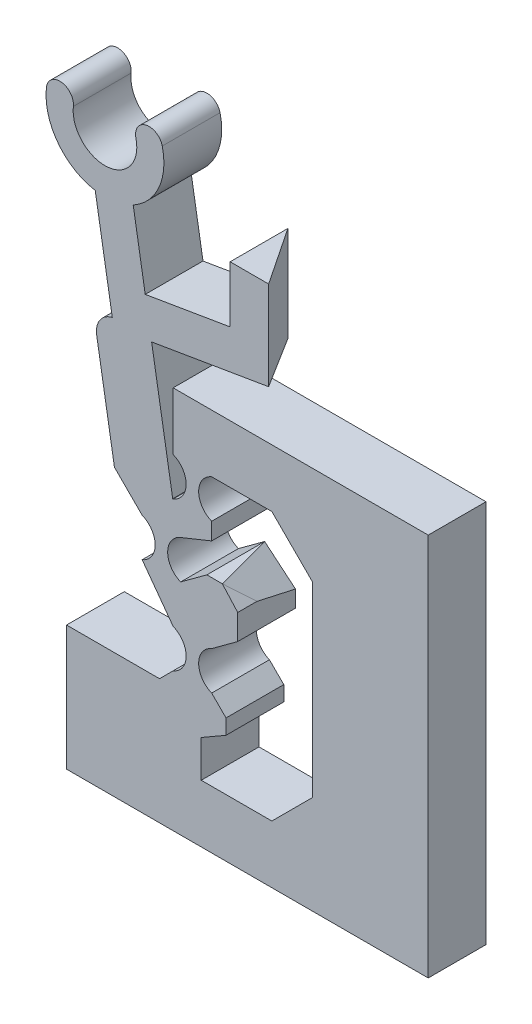
SolidWorks part; units mm, degrees
ref_plane "Front Plane" through (0, 0, 0) normal (0, 0, 1) x (1, 0, 0)
ref_plane "Top Plane" through (0, 0, 0) normal (0, 1, 0) x (1, 0, 0)
ref_plane "Right Plane" through (0, 0, 0) normal (1, 0, 0) x (0, 0, -1)
sketch "Sketch-SkeletonConfigUp" plane through (0, 0, 0) normal (0, 0, 1) x (1, 0, 0)
  line L0 (0, 0) -> (0, -50000) construction
  line L1 (0, 0) -> (4.5811, 6.2164) construction
  line L2 (9.8143, 13.3177) -> (4.5811, 13.945) construction
  line L3 (4.5811, 13.945) -> (2.9713, 10.4094) construction
  line L4 (2.9713, 10.4094) -> (4.5811, 6.2164) construction
  line L5 (4.5811, 13.945) -> (6.2429, 19.1409) construction
  line L6 (2.9713, 10.4094) -> (0.0405, 27.8193) construction
  line L7 (4.5811, 6.2164) -> (9.8143, 13.3177) construction
  line L8 (-587.3593, -797.0242) -> (9.8143, 13.3177) construction
  dimension "D2" = 7.7221
  dimension "D3" = 8.8212
  dimension "D4" = 5.2707
  dimension "D5" = 119.553
  dimension "D6" = 3.8848
  dimension "D7" = 5.4552
  dimension "D8" = 17.6549
  dimension "D9" = 4.4914
  dimension "D10" = 6.745
  dimension "D11" = 145.964
  dimension "D12" = 143.612
sketch "Sketch-SkeletonConfigDown" plane through (0, 0, 0) normal (0, 0, 1) x (1, 0, 0)
  line L0 (0, 0) -> (0, -50000) construction
  line L1 (0, 0) -> (4.5811, 6.2164) construction
  line L2 (9.8143, 13.3177) -> (4.5811, 13.945) construction
  line L3 (4.5811, 13.945) -> (6.1909, 10.4094) construction
  line L4 (6.1909, 10.4094) -> (4.5811, 6.2164) construction
  line L5 (4.5811, 13.945) -> (1.753, 18.6098) construction
  line L6 (6.1909, 10.4094) -> (-8.8652, 19.6294) construction
  line L7 (4.5811, 6.2164) -> (9.8143, 13.3177) construction
  line L8 (-589.9357, -800.5203) -> (9.8143, 13.3177) construction
  dimension "D2" = 7.7221
  dimension "D3" = 8.8212
  dimension "D4" = 5.2707
  dimension "D5" = 119.553
  dimension "D6" = 3.8848
  dimension "D7" = 5.4552
  dimension "D8" = 17.6549
  dimension "D9" = 4.4914
  dimension "D10" = 6.745
  dimension "D11" = 145.964
  dimension "D1" = 143.612
sketch "Sketch-SwitchBossUp" plane through (0, 0, 0) normal (0, 0, 1) x (1, 0, 0)
  line L0 (3.5811, 11.4759) -> (3.5811, 12.945) construction
  line L1 (5.5811, 11.1782) -> (5.5811, 12.0586) construction
  line L2 (6.5405, 22.165) -> (6.5405, 25.0939)
  line L3 (6.5405, 25.0939) -> (8.5405, 25.0939)
  line L4 (8.5405, 25.0939) -> (8.5405, 20.4736)
  line L5 (5.5811, 12.945) -> (5.5811, 12.0586)
  line L7 (1.507, 25.1315) -> (2.1313, 21.4228)
  line L8 (-0.4652, 24.7995) -> (0.4216, 19.5312)
  line L9 (2.9713, 10.4094) -> (0.0405, 27.8193) construction
  line L10 (1.9713, 9.4094) -> (3.5811, 7.2164)
  line L11 (-0.0396, 22.2712) -> (1.9326, 22.6032) construction
  line L15 (4.7006, 8.6678) -> (2.8518, 7.958) construction
  line L16 (2.9713, 10.4094) -> (4.5811, 6.2164) construction
  line L17 (3.5811, 12.945) -> (3.5811, 14.945) construction
  line L18 (5.5811, 12.945) -> (5.5811, 14.945) construction
  line L19 (4.2561, 13.945) -> (4.9061, 13.945) construction
  line L20 (3.5811, 14.945) -> (5.5811, 14.945) construction
  line L21 (3.5811, 12.945) -> (5.5811, 12.945) construction
  line L22 (4.5811, 12.945) -> (4.5811, 14.945) construction
  line L23 (4.5811, 6.2164) -> (8.5405, 7.1023) construction
  line L24 (1.9713, 9.4094) -> (1.9713, 11.4094) construction
  line L25 (3.9713, 9.4094) -> (3.9713, 11.4094) construction
  line L26 (3.9713, 9.4094) -> (1.9713, 9.4094) construction
  line L27 (1.9713, 11.4094) -> (3.9713, 11.4094) construction
  line L28 (3.5811, 7.2164) -> (5.5811, 7.2164) construction
  line L29 (3.5811, 7.2164) -> (3.5811, 5.2164) construction
  line L30 (5.5811, 7.2164) -> (5.5811, 5.2164) construction
  line L31 (3.5811, 5.2164) -> (5.5811, 5.2164) construction
  line L32 (4.9061, 6.2164) -> (4.2561, 6.2164) construction
  line L40 (3.2963, 10.4094) -> (2.6463, 10.4094) construction
  line L43 (2.874, 4.5093) -> (-1.9548, 4.5093)
  line L44 (-1.9548, 4.5093) -> (-1.9548, -1.9756)
  line L45 (-1.9548, -1.9756) -> (5.0405, -1.9756)
  line L46 (5.0405, 1.0244) -> (5.0405, 2.9474)
  line L51 (6.5405, 22.165) -> (2.1313, 21.4228)
  line L61 (6.8113, 14.945) -> (6.8113, 17.945) construction
  line L66 (0.0405, 27.8193) -> (0.0405, 50027.8193) construction
  line L74 (0.5326, 12.848) -> (-0.3888, 18.3216)
  line L75 (0.3841, 13.7302) -> (2.3564, 14.0622) construction
  line L76 (5.5811, 12.0586) -> (5.5811, 12.945) construction
  line L77 (6.7548, 8.2037) -> (5.0019, 8.2037) construction
  line L80 (6.1339, 10.409) -> (6.9354, 9.5189)
  line L81 (8.5405, 7.9632) -> (8.5405, -49992.0368) construction
  line L82 (2.1313, 21.4228) -> (3.5585, 12.945) construction
  line L83 (3.5585, 12.945) -> (2.4634, 19.4505)
  line L84 (2.4634, 19.4505) -> (8.5405, 20.4736)
  line L85 (6.9307, 9.5241) -> (8.5405, 7.7363) construction
  line L86 (5.5811, 7.2164) -> (6.9354, 8.2106)
  line L88 (3.5811, 17.945) -> (6.8113, 17.945)
  line L92 (3.7762, 8.3129) -> (6.9307, 9.5241) construction
  line L93 (6.3271, 3.6903) -> (5.0405, 2.9474)
  line L94 (3.5811, 14.945) -> (3.5811, 17.945)
  line L95 (2.1313, 21.4228) -> (2.4634, 19.4505) construction
  line L96 (2.2974, 20.4367) -> (8.5405, 21.4876) construction
  line L97 (2.2974, 20.4367) -> (1.3112, 20.2707) construction
  line L98 (6.7548, 8.2037) -> (4.7691, 10.409) construction
  line L99 (4.5811, 6.2164) -> (6.1339, 10.409) construction
  line L100 (4.5811, 6.2164) -> (8.5405, 8.2931) construction
  line L101 (4.5811, 6.2164) -> (6.9307, 9.5241) construction
  line L102 (3.5585, 12.945) -> (3.5811, 12.945)
  line L103 (8.5405, 20.4736) -> (8.5405, 8.2931) construction
  line L104 (6.9307, 9.5241) -> (8.5405, 7.7363) construction
  line L106 (6.8113, 14.945) -> (5.5811, 14.945)
  line L109 (7.3693, 7.7363) -> (8.5405, 7.7363) construction
  line L110 (8.5405, 7.7363) -> (7.3693, 7.7363) construction
  line L111 (6.9354, 9.5189) -> (6.9354, 8.2106)
  line L112 (6.9354, 9.5189) -> (6.9307, 9.5241) construction
  line L114 (7.3693, 7.7363) -> (7.3563, 7.7363) construction
  line L115 (6.8113, 17.945) -> (16.8281, 17.945)
  line L116 (16.8281, 17.945) -> (16.8281, -1.9756)
  line L117 (16.8281, -1.9756) -> (5.0405, -1.9756)
  line L118 (6.8113, 14.945) -> (8.7068, 14.945)
  line L119 (10.8281, 12.8236) -> (10.8281, 3.1457)
  line L120 (8.7068, 1.0244) -> (5.0405, 1.0244)
  line L121 (5.0405, -1.9756) -> (5.0405, 1.0244) construction
  line L122 (10.8281, 14.945) -> (13.8281, 14.945) construction
  line L123 (13.8281, 14.945) -> (16.8281, 14.945) construction
  line L124 (10.8281, 3.1457) -> (8.7068, 1.0244)
  line L125 (10.8281, 7.9847) -> (16.8281, 7.9847) construction
  line L126 (10.8281, 12.8236) -> (8.7068, 14.945)
  line L127 (8.5405, 14.945) -> (10.8281, 14.945) construction
  line L128 (10.8281, 14.945) -> (10.8281, 12.8236) construction
  line L129 (10.8281, 3.1457) -> (10.8281, 1.0244) construction
  line L130 (10.8281, 1.0244) -> (8.7068, 1.0244) construction
  line L133 (2.9713, 10.4094) -> (6.1909, 10.4094) construction
  line L134 (4.5811, 10.4094) -> (4.5811, 13.945) construction
  line L135 (4.5811, 10.4094) -> (4.5811, 6.2164) construction
  line L136 (1.9713, 11.4094) -> (0.5326, 12.848)
  line L137 (3.9713, 9.4094) -> (5.5811, 7.2164) construction
  line L138 (3.5811, 5.2164) -> (2.874, 4.5093)
  line L139 (5.333, 10.409) -> (3.9713, 9.4094)
  line L143 (4.7691, 10.409) -> (5.333, 10.409) construction
  line L144 (5.333, 10.409) -> (6.1339, 10.409)
  line L145 (4.5811, 10.4534) -> (4.7691, 10.409) construction
  line L146 (3.9713, 11.4094) -> (5.5811, 12.0586)
  line L147 (5.5811, 12.0586) -> (5.5811, 12.945) construction
  line L148 (5.5811, 5.2164) -> (6.3271, 4.4705)
  line L149 (6.3271, 4.4705) -> (6.3271, 3.6903)
  arc A0 (1.507, 25.1315) -> (3.0168, 28.5383) centre (0.0405, 27.8193) ccw
  arc A1 (-0.4652, 24.7995) -> (-3.0011, 28.1713) centre (0.0405, 27.8193) cw
  arc A2 (-3.0011, 28.1713) -> (-1.6023, 28.0095) centre (-2.3017, 28.0904) cw
  arc A3 (3.0168, 28.5383) -> (1.648, 28.2077) centre (2.3324, 28.373) ccw
  arc A4 (-1.6023, 28.0095) -> (1.648, 28.2077) centre (0.0405, 27.8193) ccw
  arc A5 (3.5811, 12.945) -> (3.5811, 14.945) centre (3.1778, 13.945) ccw
  arc A6 (5.5811, 12.945) -> (5.5811, 14.945) centre (5.9843, 13.945) cw
  arc A7 (1.9713, 9.4094) -> (1.9713, 11.4094) centre (1.568, 10.4094) ccw
  arc A8 (3.9713, 11.4094) -> (3.9713, 9.4094) centre (4.3745, 10.4094) ccw
  arc A9 (3.5811, 7.2164) -> (3.5811, 5.2164) centre (3.1779, 6.2164) cw
  arc A10 (5.5811, 7.2164) -> (5.5811, 5.2164) centre (5.9844, 6.2164) ccw
  arc A19 (-0.3888, 18.3216) -> (0.4216, 19.5312) centre (0.6565, 18.4975) cw
  arc A28 (6.21, 3.6227) -> (5.2269, 3.6539) centre (5.7492, 4.6041) cw construction
  point P44 (3.7762, 8.3129)
  point P53 (4.5811, 13.945)
  point P63 (2.9713, 10.4094)
  point P93 (0.9465, 22.4372)
  dimension "D1" = 2
  dimension "D2" = 2
  dimension "D3" = 2
  dimension "D4" = 3
  dimension "D5" = 2
  dimension "D6" = 0.65
  dimension "D7" = 2
  dimension "D8" = 42
  dimension "D9" = 3
  dimension "D10" = 5
  dimension "D11" = 8.5
  dimension "D12" = 120
  dimension "D14" = 10
  dimension "D15" = 45
  dimension "D16" = 42
  dimension "D18" = 3
  dimension "D19" = 135
  dimension "D20" = 135
  dimension "D21" = 1
  dimension "D22" = 135
extrude "Boss-SwitchMain" add sketch "Sketch-SwitchBossUp" along normal blind 3
sketch "Sketch1" plane through (0, 0, 0) normal (0, 0, -1) x (-1, 0, 0)
  line L0 (1.9548, 4.5093) -> (1.9548, -1.9756) construction
  line L1 (-4.628, -1.1895) -> (1.9548, -1.1895)
  line L2 (-4.628, -1.1895) -> (-4.628, 0.3105)
  line L3 (-4.628, 0.3105) -> (1.9548, 0.3105)
  line L4 (1.9548, -1.1895) -> (1.9548, 0.3105)
  line L5 (-3.5811, 17.945) -> (-6.6395, 17.945)
  line L6 (-2.5363, 4.5093) -> (1.9548, 4.5093)
  line L7 (-2.5363, 4.5093) -> (-2.5363, 3.0093)
  line L8 (-2.5363, 3.0093) -> (1.9548, 3.0093)
  line L9 (1.9548, 4.5093) -> (1.9548, 3.0093)
  line L10 (-6.6395, 17.945) -> (-6.8113, 16.4548)
  line L11 (-2.874, 4.5093) -> (1.9548, 4.5093) construction
  line L12 (-6.8113, 16.4548) -> (-3.5811, 16.4548)
  line L13 (-5.128, -1.3839) -> (-5.128, 7.6731) construction
  line L14 (-3.5811, 16.4548) -> (-3.5811, 17.945)
  line L18 (-3.5811, 17.945) -> (-3.5811, 14.945) construction
  line L19 (-5.128, -1.3839) -> (-5.128, 7.6731) construction
  line L20 (-6.8113, 17.945) -> (-16.8281, 17.945) construction
  line L21 (-6.8113, 14.945) -> (-6.8113, 17.945) construction
  point P15 (0, 0)
  point P16 (0, 0)
  dimension "D1" = 1.5
  dimension "D2" = 1.5
  dimension "D3" = 1.5
  dimension "D4" = 0.5
extrude "Boss-Flange Width" add sketch "Sketch1" along normal blind 6
ref_plane "Plane-Sta2Sit Groove" through (0.0405, 0, 0) normal (1, 0, 0) x (0, 0, -1)
ref_plane "Plane-Cam Face" through (-12.0395, 0, 0) normal (1, 0, 0) x (0, 0, -1)
ref_plane "Plane-FlangeTop" through (-7.0395, 0, 0) normal (1, 0, 0) x (0, 0, -1)
sketch "Sketch2" plane through (-7.0395, 0, 0) normal (1, 0, 0) x (0, 0, -1)
  line L0 (6, 16.4548) -> (0, 16.4548) construction
  line L1 (6, 17.945) -> (1, 17.945)
  line L2 (6, 17.945) -> (6, 16.4548)
  line L3 (6, 16.4548) -> (1, 16.4548)
  line L4 (1, 17.945) -> (1, 16.4548)
  line L5 (6, 3.0093) -> (0, 3.0093) construction
  line L6 (6, 4.5093) -> (1, 4.5093)
  line L7 (6, 4.5093) -> (6, 3.0093)
  line L8 (6, 3.0093) -> (1, 3.0093)
  line L9 (1, 4.5093) -> (1, 3.0093)
  line L10 (-3, -1.9756) -> (0, -1.9756) construction
  line L11 (6, 0.3105) -> (1, 0.3105)
  line L12 (6, 0.3105) -> (6, -1.9756)
  line L13 (6, -1.9756) -> (1, -1.9756)
  line L14 (1, 0.3105) -> (1, -1.9756)
  line L15 (0, 10.4094) -> (0, 27.8193) construction
  dimension "D1" = 1
extrude "Boss-Flange Height" add sketch "Sketch2" along normal up to surface (11.6675 mm away)
sketch "Sketch-HolePositions" plane through (0, -1.9756, 0) normal (0, -1, 0) x (1, 0, 0)
  line L0 (-7.0395, -3.5) -> (4.628, -3.5) construction
  line L2 (4.628, -1) -> (4.628, 0) construction
  line L3 (4.628, -1) -> (-7.0395, -1) construction
  line L4 (-7.0395, -22.2167) -> (-7.0395, 22.2167) construction
  point P6 (-4.0395, -3.5)
  point P7 (1.628, -3.5)
  dimension "D1" = 3
  dimension "D2" = 3
  dimension "D3" = 2.5
sketch "Sketch6" plane through (0, -1.9756, 0) normal (0, -1, 0) x (-1, 0, 0)
  point P0 (4.0395, 3.5)
  point P3 (-1.628, 3.5)
hole_wizard "Tap Drill for M2x0.4 Tap1" positions "Sketch6" profile "Sketch5" hole size "M2x0.4" standard "ANSI Metric" end condition through all
sketch "Sketch5" plane through (-4.0395, -1.9756, -3.5) normal (1, 0, 0) x (0, 0, -1)
  line L0 (0, 0) -> (0, 31.0527)
  line L1 (0, 31.0527) -> (0.8, 31.0527)
  line L2 (0.8, 31.0527) -> (0.8, 0)
  line L5 (0.8, 0) -> (0, 0)
  line L11 (0, -6.35) -> (0, 107.95) construction
  dimension "Thru Hole Dia." = 1.6
  dimension "Thru Hole Depth" = 31.0527
sketch "Sketch9" plane through (0, -1.9756, 0) normal (0, -1, 0) x (1, 0, 0)
  point P0 (-4.0395, -3.5)
  point P3 (1.628, -3.5)
hole_wizard "M2 Clearance Hole2" positions "Sketch9" profile "Sketch8" hole size "M2" standard "ANSI Metric"
sketch "Sketch8" plane through (-4.0395, -1.9756, -3.5) normal (1, 0, 0) x (0, 0, -1)
  line L0 (0, 0) -> (0, 7.206)
  line L1 (0, 7.206) -> (1.2, 6.4849)
  line L2 (1.2, 6.4849) -> (1.2, 0)
  line L5 (1.2, 0) -> (0, 0)
  line L10 (0, 7.206) -> (-1.2, 6.4849) construction
  line L11 (0, -6.35) -> (0, 107.95) construction
  dimension "Hole Dia." = 2.4
  dimension "Hole Depth" = 6.4849
  dimension "Drill Angle" = 118
sketch "Sketch10" plane through (0, 17.945, 0) normal (0, 1, 0) x (1, 0, 0)
  line L1 (6.6395, 6) -> (5.128, 6)
  line L2 (6.6395, 6) -> (6.6395, 3)
  line L3 (6.6395, 3) -> (5.128, 3)
  line L5 (4.628, 7) -> (4.628, 1) construction
  line L6 (3.5811, 1) -> (-7.0395, 1) construction
  line L7 (5.128, 6.25) -> (5.128, 1) construction
  line L8 (5.128, 6) -> (5.128, 3)
  dimension "D1" = 2
extrude "Cut-Flange Ramp Clearance" cut sketch "Sketch10" against normal up to next
sketch "Sketch-Measurements for Derailleur Ramps" plane through (0, 0, 0) normal (0, 0, 1) x (1, 0, 0)
  line L0 (2.4634, 19.4505) -> (2.1313, 21.4228)
  line L1 (2.2974, 20.4367) -> (1.3112, 20.2707)
  line L2 (2.9713, 10.4094) -> (0.0405, 27.8193) construction
  line L3 (1.3112, 20.2707) -> (-4.0257, 16.6658)
  line L4 (6.1909, 10.4094) -> (-8.8652, 19.6294) construction
  line L5 (1.3112, 20.2707) -> (2.6012, 12.6077)
  line L6 (2.6012, 12.6077) -> (-4.0257, 16.6658)
  line L7 (-1.3573, 18.4682) -> (-1.3573, 20.2707)
  line L8 (-1.3573, 20.2707) -> (1.3112, 20.2707)
  line L9 (6.1909, 10.4094) -> (2.9713, 10.4094)
  line L10 (5.386, 8.3129) -> (3.7762, 8.3129)
  line L12 (6.1909, 10.4094) -> (4.5811, 6.2164) construction
  line L13 (4.5811, 8.3129) -> (4.5811, 8.7912)
  line L14 (4.5811, 6.2164) -> (5.386, 8.3129)
  line L15 (2.9713, 10.4094) -> (4.5811, 6.2164) construction
  line L16 (3.7762, 8.3129) -> (4.5811, 6.2164)
  line L17 (5.386, 8.3129) -> (5.386, 8.7912)
  dimension "D1" = 2.6685
  dimension "D2" = 0.8049
sketch "Sketch12" plane through (0, 25.0939, 0) normal (0, 1, 0) x (1, 0, 0)
  line L0 (6.5405, 0) -> (8.5405, -3)
  line L1 (8.5405, -3) -> (8.5405, 0)
  line L2 (8.5405, 0) -> (6.5405, 0)
extrude "Cut-Extrude1" cut sketch "Sketch12" against normal up to next
ref_plane "Plane1" through (0, 7.1023, 0) normal (0, 1, 0) x (1, 0, 0)
sketch "Sketch-Derailleur Location" plane through (0, 7.1023, 0) normal (0, 1, 0) x (1, 0, 0)
  line L0 (8.5405, 0) -> (8.5405, -3)
  line L1 (3.5811, -3) -> (4.2561, -3) construction
  line L2 (-119237.4187, 0) -> (9.8143, 0) construction
  point P0 (8.5405, 0)
  point P5 (8.5405, 0)
  point P8 (8.5405, -1.5)
ref_plane "Plane-Cantilever Cut" through (7.0973, 8.5173, -1.8949) normal (-0.631, -0.7573, 0.1685) x (-0.7758, 0.616, -0.137)
sketch "Sketch14" plane through (7.0973, 8.5173, -1.8949) normal (-0.631, -0.7573, 0.1685) x (-0.7758, 0.616, -0.137)
  line L0 (2.5653, -1.6911) -> (-0.4368, -1.6911)
  line L2 (2.5653, -5.3731) -> (2.5653, -1.6911)
  line L3 (-0.4368, -1.6911) -> (-0.4368, -5.3731)
  line L4 (-0.4368, -5.3731) -> (2.5653, -5.3731)
  point P4 (3.3309, -1.68)
  point P6 (3.3309, -5.3488)
  point P8 (-0.4368, -1.68)
  point P9 (2.5653, -5.3731)
  point P10 (2.7763, -1.6972)
extrude "Cut-Extrude2" cut sketch "Sketch14" against normal up to next
sketch "Sketch15" plane through (0, 0, 0) normal (0, 0, -1) x (-1, 0, 0)
  line L1 (-10.0534, 18.2157) -> (8.3706, 18.2157)
  line L2 (-10.0534, 18.2157) -> (-10.0534, -2.1599)
  line L3 (-10.0534, -2.1599) -> (8.3706, -2.1599)
  line L4 (8.3706, 18.2157) -> (8.3706, -2.1599)
extrude "Cut-Extrude3" cut sketch "Sketch15" along normal through all
equation "\"axle-diameter\"=2"
equation "\"switch-thickness\"=12"
equation "\"base-width\"=4.0"
equation "\"axle-bushing-radius\"=3"
equation "\"clearance\"= 0.25"
equation "\"arm-width\"=1.5"
equation "\"min-diameter\"=70"
equation "\"alpha\"=143.6120"
equation "\"gamma\"=119.5526"
equation "\"delta\"=145.9637"
equation "\"epsilon\"=6.7452"
equation "\"l_AB\"=8.8212"
equation "\"l_AC\"=4.4914"
equation "\"l_BD\"=5.2707"
equation "\"l_CD\"=3.8848"
equation "\"l_CE\"=17.6549"
equation "\"l_DF\"=5.4552"
equation "\"l_OA\"=7.7221"
equation "\"D2@Sketch-SkeletonConfigUp\" = \"l_OA\""
equation "\"D3@Sketch-SkeletonConfigUp\" = \"l_AB\""
equation "\"D4@Sketch-SkeletonConfigUp\" = \"l_BD\""
equation "\"D5@Sketch-SkeletonConfigUp\" = \"gamma\""
equation "\"D6@Sketch-SkeletonConfigUp\" = \"l_CD\""
equation "\"D7@Sketch-SkeletonConfigUp\" = \"l_DF\""
equation "\"D8@Sketch-SkeletonConfigUp\" = \"l_CE\""
equation "\"D9@Sketch-SkeletonConfigUp\" = \"l_AC\""
equation "\"D_groove\"=3.175"
equation "\"D7@Sketch-SkeletonConfigDown\" = \"l_DF\""
equation "\"D6@Sketch-SkeletonConfigDown\" = \"l_CD\""
equation "\"D2@Sketch-SkeletonConfigDown\" = \"l_OA\""
equation "\"D3@Sketch-SkeletonConfigDown\" = \"l_AB\""
equation "\"D9@Sketch-SkeletonConfigDown\" = \"l_AC\""
equation "\"D8@Sketch-SkeletonConfigDown\" = \"l_CE\""
equation "\"D5@Sketch-SkeletonConfigDown\" = \"gamma\""
equation "\"D4@Sketch-SkeletonConfigDown\" = \"l_BD\""
equation "\"D1@Sketch-SkeletonConfigDown\" = \"alpha\""
equation "\"hinge_length\"=1.5"
equation "\"hinge_depth\"=0.25"
equation "\"D10@Sketch-SkeletonConfigUp\"=\"epsilon\""
equation "\"D11@Sketch-SkeletonConfigUp\"=\"delta\""
equation "\"D12@Sketch-SkeletonConfigUp\"=\"alpha\""
equation "\"D11@Sketch-SkeletonConfigDown\"=\"delta\""
equation "\"D10@Sketch-SkeletonConfigDown\"=\"epsilon\""
equation "\"EE_dx\"=8.9056"
equation "\"EE_dy\"=8.1898"
equation "\"r_groove\"=\"D_groove\"/2"
equation "\"t_wall\"=25.4/16"
equation "\"width_lower\"=\"D_groove\"+\"t_wall\""
equation "\"cable_to_bottom\"=30.6257"
equation "\"switch_EE-up_base_dy\"=24"
equation "\"switch_EE-down_base_dy\"=16"
equation "\"D_axle\"=25.4/8"
equation "\"D_up_to_down\"=16"
equation "\"D_down_to_up\"=25"
equation "\"t_cam_base\"=7.5"
